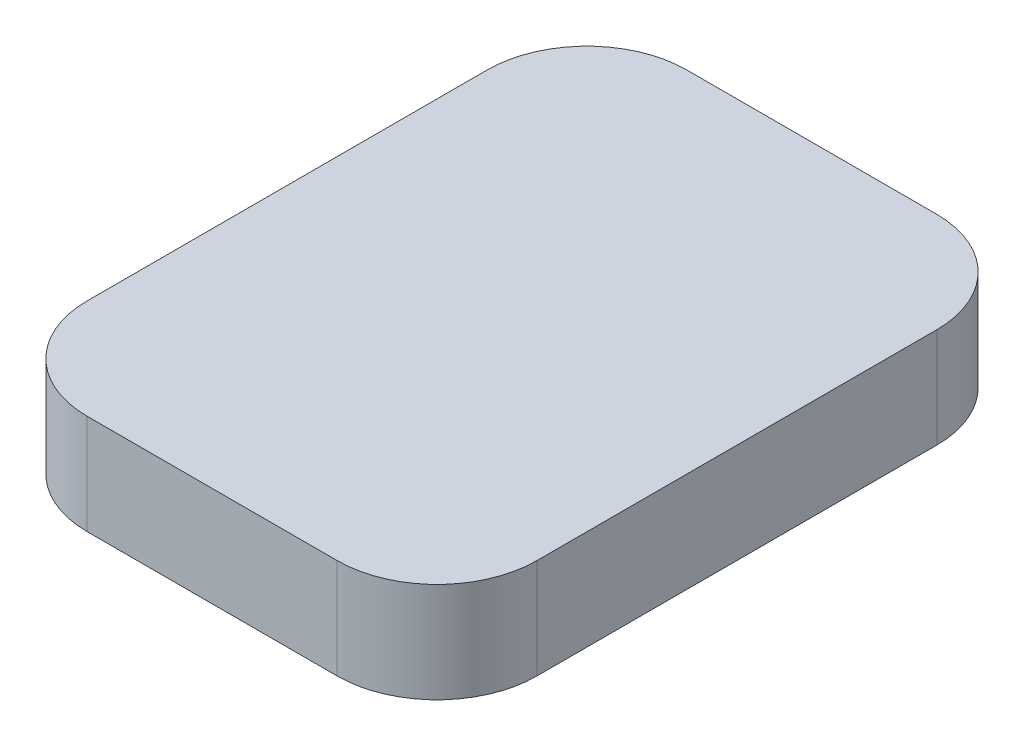
SolidWorks part; units mm, degrees
ref_plane "Plan de face" through (0, 0, 0) normal (0, 0, 1) x (1, 0, 0)
ref_plane "Plan de dessus" through (0, 0, 0) normal (0, 1, 0) x (1, 0, 0)
ref_plane "Plan de droite" through (0, 0, 0) normal (1, 0, 0) x (0, 0, -1)
sketch "Esquisse2" plane through (0, 0, 0) normal (0, 1, 0) x (1, 0, 0)
  line L1 (-12.5, 30) -> (12.5, 30)
  line L2 (-22.5, 20) -> (-22.5, -20)
  line L3 (-12.5, -30) -> (12.5, -30)
  line L4 (22.5, 20) -> (22.5, -20)
  arc A0 (12.5, 30) -> (22.5, 20) centre (12.5, 20) cw
  arc A1 (12.5, -30) -> (22.5, -20) centre (12.5, -20) ccw
  arc A2 (-22.5, -20) -> (-12.5, -30) centre (-12.5, -20) ccw
  arc A3 (-12.5, 30) -> (-22.5, 20) centre (-12.5, 20) ccw
  point P4 (-22.5, 0)
  point P6 (0, 30)
  point P9 (22.5, 30)
  point P14 (-22.5, -30)
  point P17 (-22.5, 30)
  dimension "D3" = 10
  dimension "D1" = 45
  dimension "D2" = 60
extrude "Boss.-Extru.1" add sketch "Esquisse2" along normal blind 10 contours L2 A2 L3 A1 L4 A0 L1 A3
